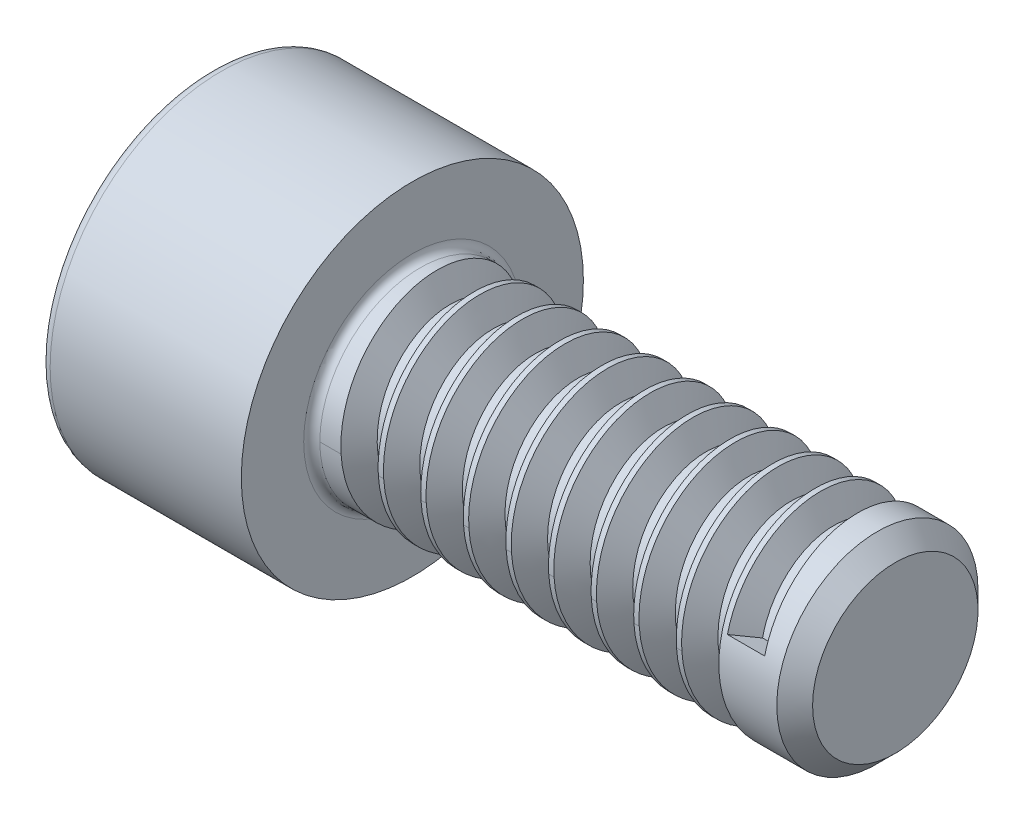
SolidWorks part; units mm, degrees
revolve "Base-Revolve" add sketch "BodySke"
sketch "BodySke" plane through (0, 0, 0) normal (0, 0, 1) x (1, 0, 0)
  line L0 (0, 0) -> (0, 4.25)
  line L1 (0, 4.25) -> (5, 4.25)
  line L2 (5, 4.25) -> (5, 2.5)
  line L3 (5, 2.5) -> (16.555, 2.5)
  line L4 (17, 2.055) -> (17, 0)
  line L5 (17, 0) -> (0, 0)
  line L6 (-31.75, 0) -> (127, 0) construction
  line L8 (17, 2.055) -> (16.555, 2.5)
  line L10 (17, -2.055) -> (16.555, -2.5) construction
  line L11 (5.8, 9.525) -> (5.8, 3.175) construction
  line L12 (5, 9.525) -> (5, 3.175) construction
  line L13 (-43, 9.525) -> (-43, 3.175) construction
  dimension "Diameter" = 5
  dimension "Head_dia" = 8.5
cosmetic thread "ThreadCosmetic" [suppressed]
fillet "Fillet1" radius 0.2 1 edges at (5, 0, 2.5)
fillet "Fillet2" radius 0.25 1 edges at (0, 0, 4.25)
ref_plane "Plane1" through (0, 0, 0) normal (0, 0, 1) x (1, 0, 0)
ref_plane "Plane2" through (0, 0, 0) normal (0, 1, 0) x (1, 0, 0)
ref_plane "Plane3" through (0, 0, 0) normal (1, 0, 0) x (0, 0, -1)
sketch "Sketch2" plane through (0, 0, 0) normal (0, 0, 1) x (1, 0, 0)
  line L0 (0, 2.042) -> (2.5, 2.042)
  line L1 (2.5, 2.042) -> (3.6789, 0)
  line L2 (-31.75, 0) -> (127, 0) construction
  line L3 (3.6789, 0) -> (0, 0)
  line L4 (0, 0) -> (0, 2.042)
  line L6 (0, 0) -> (47.625, 0) construction
  dimension "D1" = 2.042
  dimension "D2" = 60
revolve "Hex-PreBroach" cut sketch "Sketch2" angle 360 about L6
sketch "Sketch3" plane through (0, 0, 0) normal (-1, 0, 0) x (0, 0.5, 0.866)
  line L0 (1.1789, 2.042) -> (-1.1789, 2.042)
  line L1 (-1.1789, 2.042) -> (-2.3579, 0)
  line L2 (1.1789, 2.042) -> (2.3579, 0)
  line L3 (1.1789, -2.042) -> (2.3579, 0)
  line L4 (1.1789, -2.042) -> (-1.1789, -2.042)
  line L5 (-1.1789, -2.042) -> (-2.3579, 0)
  dimension "D1" = 2.042
  dimension "D2" = 2.042
extrude "Hex" cut sketch "Sketch3" against normal blind 2.5
sketch "ThdSchSke" plane through (0, 0, 0) normal (0, 0, 1) x (1, 0, 0)
  line L0 (7.4, -2.055) -> (7.0884, -2.5)
  line L1 (7.4, -2.055) -> (7.7116, -2.5)
  line L2 (7.7116, -2.5) -> (7.7116, -3.125)
  line L3 (-3.175, 0) -> (5.1513, 0) construction
  line L4 (0, 4) -> (0, -4) construction
  line L5 (7.7116, -3.125) -> (7.0884, -3.125)
  line L6 (7.0884, -3.125) -> (7.0884, -2.5)
  dimension "Diameter" = 5
  dimension "Thread_minor" = 4.11
  dimension "Start" = 7.4
revolve "ThreadSchematic" [suppressed] cut sketch "ThdSchSke" angle 360 about L3
pattern_linear "ThdSchPat" [suppressed]
thread "螺纹线1" pitch 1.0583 method cut profile "螺纹线轮廓1" start angle 0, offset 0, length 10, pitch 1.0583, diameter 5
ref_plane "基准面1" through (5.2, 0, -2.5) normal (0, -1, 0) x (0, 0, -1)
sketch "螺纹线轮廓1" plane through (5.2, 0, -2.5) normal (0, -1, 0) x (0, 0, -1)
  line L0 (0, 0) -> (0, 1.0583) construction
  line L11 (0, 0) -> (0, 0.926)
  line L12 (0, 0.926) -> (-0.5728, 0.5953)
  line L13 (-0.5728, 0.5953) -> (-0.5728, 0.3307)
  line L15 (-0.5728, 0.3307) -> (0, 0)
  line L17 (-0.5728, 0.463) -> (0, 0.463) construction
  point P2 (0, 0)
  dimension "Pitch" = 1.0583
  dimension "Profile_Angle" = 60
  dimension "Profile_Land" = 0.2646
  dimension "Profile_Height" = 0.5728
equation "\"D2@Sketch3\" = \"Hex_size@Sketch3\" / 2"
equation "\"D1@Sketch3\" = \"Hex_size@Sketch3\" / 2"
equation "\"D1@Sketch2\" = \"Hex_size@Sketch3\" / 2"
equation "\"Thread_minor@ThreadCosmetic\"  =  \"Minor_dia@BodySke\""
equation "\"Depth@Sketch2\" =  \"Key_eng@Hex\""
equation "\"Thread_length@ThreadCosmetic\" = ((sgn( (\"Length@BodySke\" - \"Advance@BodySke\" * 3.0) - \"Thread_nom@BodySke\" )-1)*( (\"Length@BodySke\" - \"Advance@BodySke\" * 3.0) - \"Thread_nom@BodySke\" ))/-2+ \"Thread_nom@BodySke\""
equation "\"Thread_minor@ThdSchSke\" = \"Minor_dia@BodySke\""
equation "\"Diameter@ThdSchSke\" = \"Diameter@BodySke\""
equation "\"Overcut@ThdSchSke\" = \"Diameter@BodySke\" * 1.25"
equation "\"Start@ThdSchSke\" = \"Head_ht@BodySke\" + \"Length@BodySke\" - \"Thread_length@ThreadCosmetic\"  '---Non-countersunk---"
equation "\"Num_threads@ThdSchPat\" = int( \"Thread_length@ThreadCosmetic\" / \"Advance@BodySke\" + 0.999 )  + 1"
equation "\"Advance@ThdSchPat\" = \"Thread_length@ThreadCosmetic\" /  (\"Num_threads@ThdSchPat\" - 1) 'relax it"
equation "\"Num_threads@ThdSchPat\" = \"Num_threads@ThdSchPat\" - sgn( \"Num_threads@ThdSchPat\" - 1) '---chamfered tips only---"
